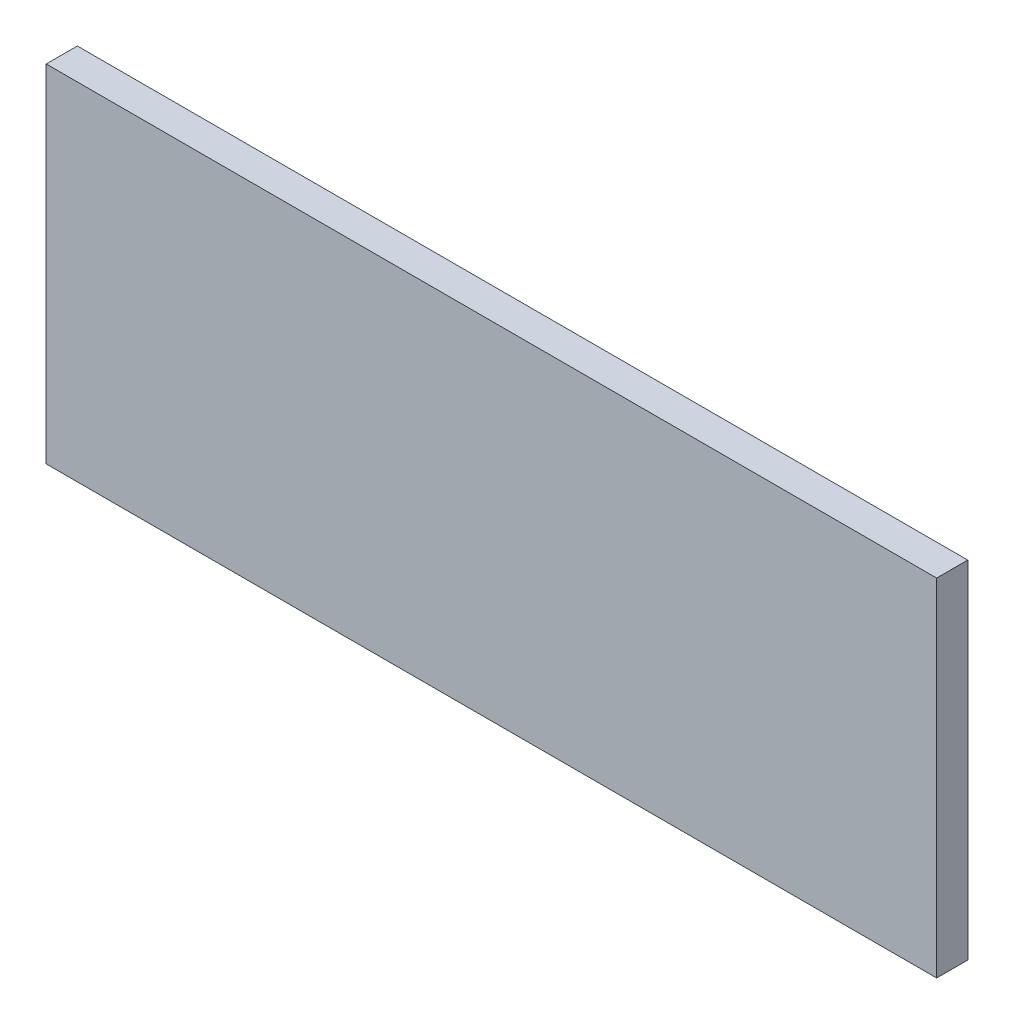
SolidWorks part; units mm, degrees
ref_plane "Front Plane" through (0, 0, 0) normal (0, 0, 1) x (1, 0, 0)
ref_plane "Top Plane" through (0, 0, 0) normal (0, 1, 0) x (1, 0, 0)
ref_plane "Right Plane" through (0, 0, 0) normal (1, 0, 0) x (0, 0, -1)
sketch "Sketch1" plane through (0, 0, 0) normal (0, 0, 1) x (1, 0, 0)
  line L1 (0, 0) -> (72.6741, 0)
  line L2 (0, 0) -> (0, 28.2712)
  line L3 (0, 28.2712) -> (72.6741, 28.2712)
  line L4 (72.6741, 0) -> (72.6741, 28.2712)
extrude "Boss-Extrude1" add sketch "Sketch1" along normal blind 2.54
